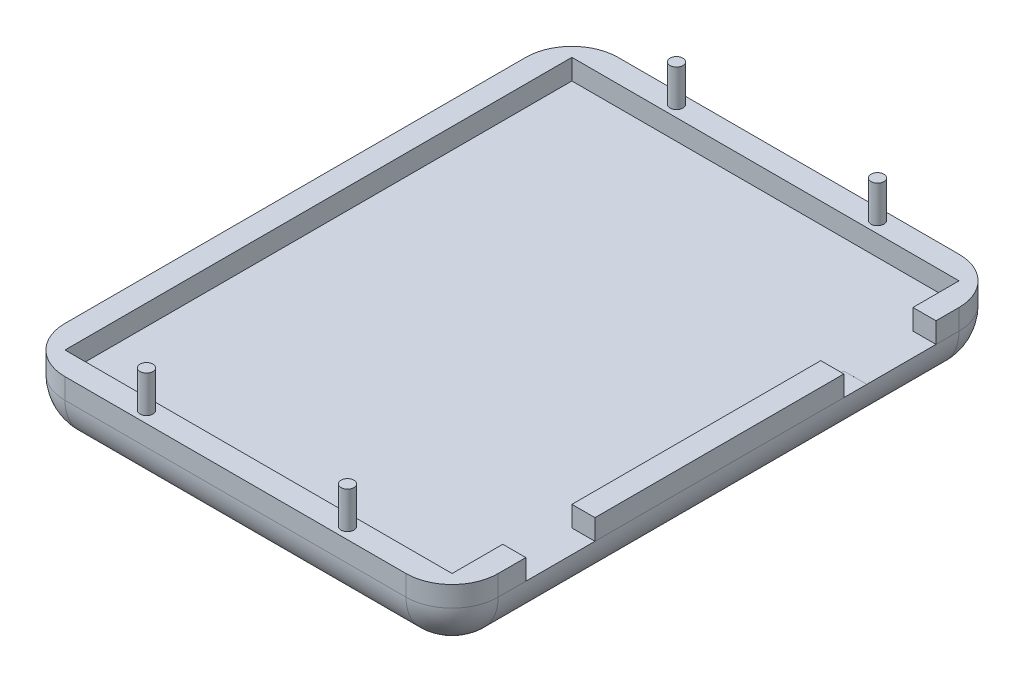
SolidWorks part; units mm, degrees
ref_plane "정면" through (0, 0, 0) normal (0, 0, 1) x (1, 0, 0)
ref_plane "윗면" through (0, 0, 0) normal (0, 1, 0) x (1, 0, 0)
ref_plane "우측면" through (0, 0, 0) normal (1, 0, 0) x (0, 0, -1)
sketch "스케치1" plane through (0, 0, 0) normal (0, 0, 1) x (1, 0, 0)
  line L0 (0, 0) -> (94, 0)
  line L1 (0, 0) -> (0, 30)
  line L2 (0, 30) -> (94, 30)
  line L3 (94, 30) -> (94, 0)
  dimension "D1" = 94
  dimension "D2" = 30
extrude "보스-돌출2" add sketch "스케치1" along normal blind 120 contours L2 L3 L0 L1
sketch "스케치2" plane through (0, 30, 0) normal (0, 1, 0) x (1, 0, 0)
  line L0 (47, 0) -> (47, -120) construction
  line L1 (0, 0) -> (94, 0) construction
  line L2 (0, -120) -> (94, -120) construction
  line L3 (0, -60) -> (94, -60) construction
  line L4 (0, -120) -> (0, 0) construction
  line L5 (94, -120) -> (94, 0) construction
  line L7 (5, -115) -> (89, -115)
  line L8 (5, -115) -> (5, -5)
  line L9 (5, -5) -> (89, -5)
  line L10 (89, -115) -> (89, -5)
  line L11 (47, -5) -> (47, -115) construction
  line L12 (5, -60) -> (89, -60) construction
  point P12 (47, -60)
  dimension "D1" = 84
  dimension "D2" = 110
extrude "컷-돌출1" cut sketch "스케치2" against normal blind 20 contours L9 L10 L7 L8
sketch "스케치4" plane through (0, 30, 0) normal (0, 1, 0) x (1, 0, 0)
  line L2 (89, -115) -> (89, -5) construction
  line L3 (0, -120) -> (0, 0) construction
  line L4 (89, -15) -> (100.6987, -15)
  line L5 (89, -15) -> (89, -27.228)
  line L6 (89, -27.228) -> (100.6987, -27.228)
  line L7 (100.6987, -15) -> (100.6987, -27.228)
  line L8 (0, -120) -> (94, -120) construction
  line L11 (89, -104) -> (101.8042, -104)
  line L12 (89, -104) -> (89, -84)
  line L13 (89, -84) -> (101.8042, -84)
  line L14 (101.8042, -104) -> (101.8042, -84)
  dimension "D1" = 94
  dimension "D2" = 94
  dimension "D3" = 100.6987
  dimension "D4" = 92.772
  dimension "D5" = 101.8042
  dimension "D6" = 20
  dimension "D7" = 16
  dimension "D8" = 105
  dimension "D9" = 120
extrude "컷-돌출5" cut sketch "스케치4" against normal blind 20 contours L13 L14 L11 L12
ref_plane "평면2" through (94, 30, 0) normal (1, 0, 0) x (0, 0, -1)
sketch "스케치9" plane through (0, 30, 0) normal (0, 1, 0) x (1, 0, 0)
  line L0 (0, -120) -> (0, 0) construction
  line L2 (89, -84) -> (89, -5) construction
  line L3 (0, -120) -> (94, -120) construction
  line L4 (89, -15) -> (106.0344, -15)
  line L5 (89, -15) -> (89, -30)
  line L6 (89, -30) -> (106.0344, -30)
  line L7 (106.0344, -15) -> (106.0344, -30)
  dimension "D1" = 94
  dimension "D2" = 15
  dimension "D3" = 106.0344
  dimension "D4" = 90
  dimension "D5" = 120
extrude "컷-돌출6" cut sketch "스케치9" against normal blind 20
sketch "스케치10" plane through (0, 0, 0) normal (0, -1, 0) x (-1, 0, 0)
  line L0 (-94, -120) -> (-60, -76.8831)
  line L2 (0, 0) -> (-94, 0) construction
  line L3 (-60, -42.8831) -> (-94, 0)
  line L4 (-34, -76.8831) -> (0, -120)
  line L5 (-34, -42.8831) -> (0, 0)
  line L7 (-34, -42.8831) -> (-60, -42.8831)
  line L8 (-34, -42.8831) -> (-34, -76.8831)
  line L9 (-34, -76.8831) -> (-60, -76.8831)
  line L10 (-60, -42.8831) -> (-60, -76.8831)
  point P12 (-47, -60)
  dimension "D1" = 26
  dimension "D2" = 42.8831
  dimension "D4" = 34
extrude "돌출-얇게2" add sketch "스케치10" along normal blind 26 thin contours L9 thin type one direction wall 34
ref_plane "평면3" through (0, 0, 0) normal (1, 0, 0) x (0, 0, -1)
sketch "스케치16" plane through (0, 0, 42.8831) normal (0, 0, -1) x (-1, 0, 0)
  line L0 (-60, -13) -> (-34, -13) construction
  line L1 (-60, -26) -> (-60, 0) construction
  line L2 (-34, -26) -> (-34, 0) construction
  line L3 (-47, 0) -> (-47, -26) construction
  line L4 (-34, 0) -> (-60, 0) construction
  line L5 (-34, -26) -> (-60, -26) construction
  circle A0 centre (-47, -13) radius 11.5
  dimension "D1" = 23
extrude "컷-돌출8" cut sketch "스케치16" against normal through all contours A0
fillet "필렛2" radius 10 1 edges at (0, 15, 0)
fillet "필렛3" radius 10 3 edges at (0, 15, 120) (94, 15, 120) (94, 15, 0)
fillet "필렛4" radius 10 8 edges at (2.9289, 0, 2.9289) (0, 0, 60) (2.9289, 0, 117.0711) (47, 0, 120) (91.0711, 0, 117.0711) (94, 0, 60) (91.0711, 0, 2.9289) (47, 0, 0)
sketch "스케치20" plane through (0, 30, 0) normal (0, 1, 0) x (1, 0, 0)
  line L0 (0, -110) -> (0, -10) construction
  circle A0 centre (25.1928, -2.5) radius 1.5
  circle A1 centre (68.8072, -2.5) radius 1.5
  circle A2 centre (25.1928, -117.5) radius 1.5
  circle A3 centre (68.8072, -117.5) radius 1.5
  dimension "D1" = 3
  dimension "D2" = 3
  dimension "D3" = 25.1928
  dimension "D4" = 68.8072
  dimension "D5" = 105
  dimension "D6" = 112.5
  dimension "D7" = 2.5
extrude "컷-돌출12" cut sketch "스케치20" against normal blind 10 contours A0 | A2 | A3 | A1
sketch "스케치21" plane through (0, 0, 76.8831) normal (0, 0, 1) x (1, 0, 0)
  line L0 (34, -26) -> (34, 0) construction
  line L1 (34, 0) -> (62.8648, 0)
  line L2 (34, 0) -> (34, -27.7873)
  line L3 (34, -27.7873) -> (62.8648, -27.7873)
  line L4 (62.8648, 0) -> (62.8648, -27.7873)
extrude "컷-돌출13" cut sketch "스케치21" against normal blind 40 contours L2 L3 L4 L1
sketch "스케치22" plane through (5, 0, 0) normal (1, 0, 0) x (0, 0, -1)
  line L0 (0, 30) -> (0, 10) construction
  line L1 (-124.7071, 32.5635) -> (0, 32.5635)
  line L2 (-124.7071, 32.5635) -> (-124.7071, 14.4465)
  line L3 (-124.7071, 14.4465) -> (0, 14.4465)
  line L4 (0, 32.5635) -> (0, 14.4465)
  point P6 (-124.7071, 14.4465)
extrude "컷-돌출14" cut sketch "스케치22" along normal blind 150 from offset 50 contours L1 L4 L3 L2 offset against normal yes
sketch "스케치23" plane through (0, 14.4465, 0) normal (0, 1, 0) x (1, 0, 0)
  line L0 (47, -115) -> (47, -120) construction
  line L1 (5, -115) -> (89, -115) construction
  line L2 (10, -120) -> (84, -120) construction
  line L5 (47, -117.5) -> (90.6144, -117.5) construction
  line L6 (47, -117.5) -> (3.3856, -117.5) construction
  circle A0 centre (25.1928, -117.5) radius 1.4
  circle A1 centre (68.8072, -117.5) radius 1.4
  circle A2 centre (25.1928, -2.5) radius 1.4
  circle A3 centre (68.8072, -2.5) radius 1.4
  arc A4 (84, -120) -> (94, -110) centre (84, -110) ccw construction
  arc A5 (0, -110) -> (10, -120) centre (10, -110) ccw construction
  dimension "D1" = 2.8
  dimension "D2" = 2.8
extrude "보스-돌출4" add sketch "스케치23" along normal blind 8 contours A0 | A1 | A3 | A2
sketch "스케치25" plane through (0, 14.4465, 0) normal (0, 1, 0) x (1, 0, 0)
  line L2 (94, -55) -> (94, 55) construction
  line L3 (89, -30) -> (94, -30)
  line L4 (89, -30) -> (89, -35)
  line L5 (89, -35) -> (94, -35)
  line L6 (94, -30) -> (94, -35)
  dimension "D1" = 5
extrude "컷-돌출15" cut sketch "스케치25" against normal blind 4.45 contours L3 L6 L5 L4
ref_plane "평면4" through (94, 9.9965, 30) normal (1, 0, 0) x (0, 0, -1)
sketch "스케치28" plane through (0, 14.4465, 0) normal (0, 1, 0) x (1, 0, 0)
  line L0 (94, -55) -> (94, 55) construction
  line L1 (89, -84) -> (94, -84)
  line L2 (89, -84) -> (89, -89)
  line L3 (89, -89) -> (94, -89)
  line L4 (94, -84) -> (94, -89)
  dimension "D1" = 5
extrude "보스-돌출5" add sketch "스케치28" against normal blind 4.45 contours L2 L3 L4 L1
